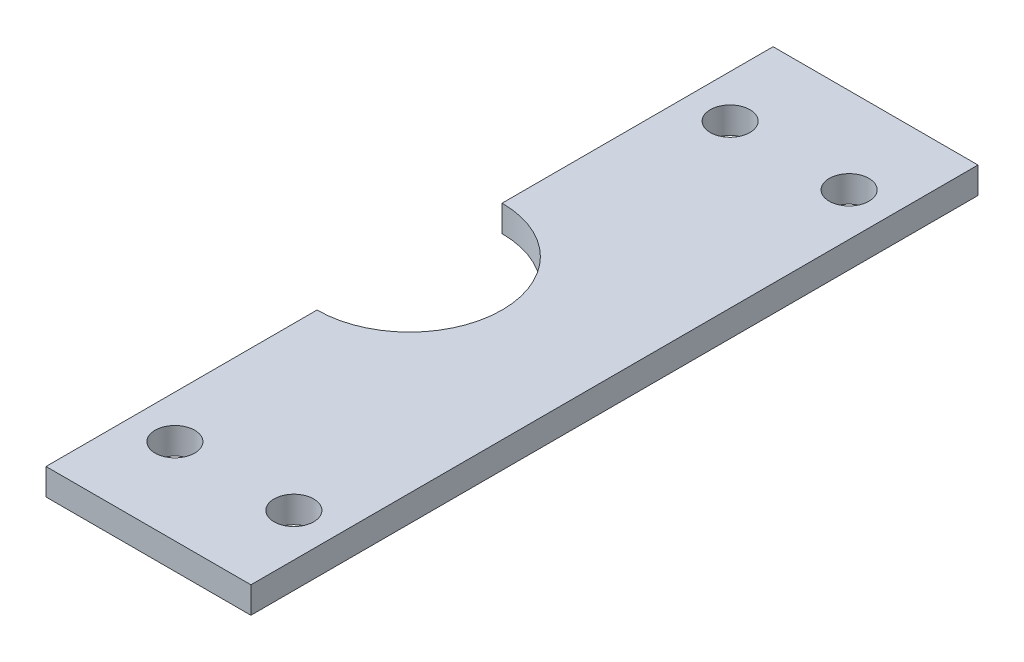
SolidWorks part; units mm, degrees
material "3.0205 (EN-AW 1200)"
ref_plane "Plan de face" through (0, 0, 0) normal (0, 0, 1) x (1, 0, 0)
ref_plane "Plan de dessus" through (0, 0, 0) normal (0, 1, 0) x (1, 0, 0)
ref_plane "Plan de droite" through (0, 0, 0) normal (1, 0, 0) x (0, 0, -1)
sketch "Esquisse1" plane through (0, 0, 0) normal (0, 0, 1) x (1, 0, 0)
  line L1 (0, 0) -> (15.5, 0)
  dimension "D2" = 15.5
extrude "Extru.-Mince1" add sketch "Esquisse1" along normal blind 55 thin thin type one direction reverse wall 2
sketch "Esquisse2" plane through (0, 2, 0) normal (0, 1, 0) x (1, 0, 0)
  line L0 (0, -27.5) -> (7.75, -27.5) construction
  line L1 (0, -55) -> (0, 0) construction
  line L2 (7.75, -27.5) -> (7.75, 0) construction
  line L3 (0, 0) -> (15.5, 0) construction
  line L4 (15.5, -55) -> (15.5, 0) construction
  circle A0 centre (3.25, -6.5) radius 1.5
  circle A1 centre (12.25, -6.5) radius 1.5
  circle A2 centre (12.25, -48.5) radius 1.5
  circle A3 centre (3.25, -48.5) radius 1.5
  circle A4 centre (0, -27.5) radius 7
  point P8 (7.75, 0)
  dimension "D1" = 42
  dimension "D2" = 9
  dimension "D3" = 3
  dimension "D4" = 14
  dimension "D5" = 6.5
  dimension "D6" = 3.25
extrude "Enlèv. mat.-Extru.1" cut sketch "Esquisse2" against normal through all
